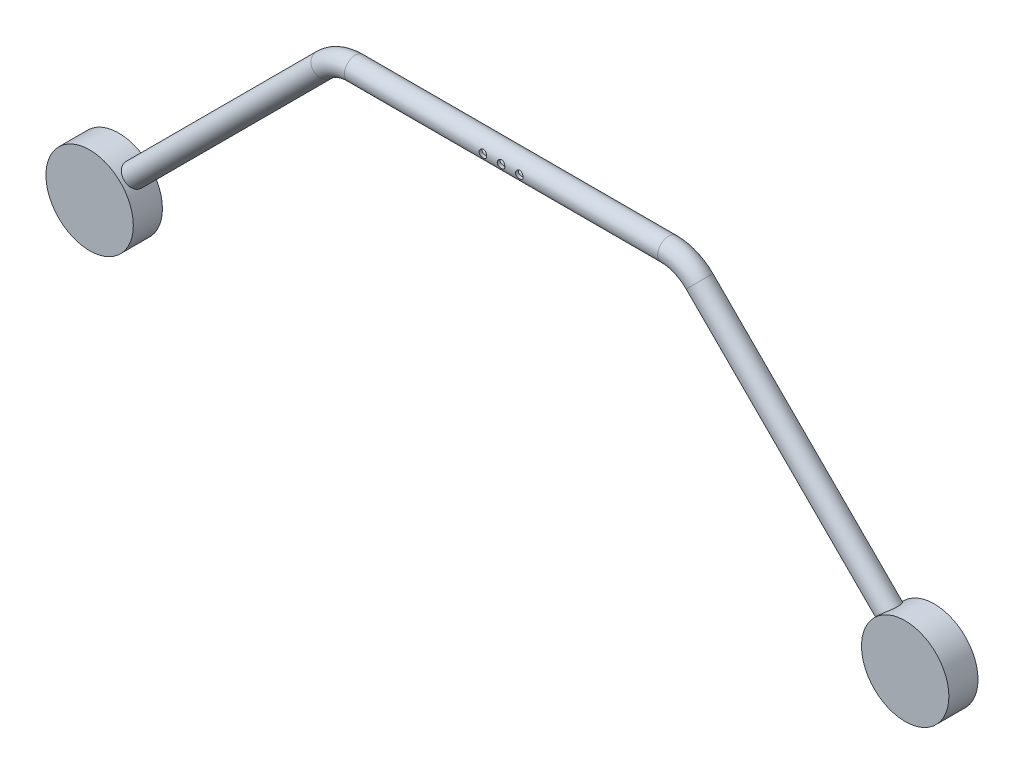
SolidWorks part; units mm, degrees
ref_plane "Front Plane" through (0, 0, 0) normal (0, 0, 1) x (1, 0, 0)
ref_plane "Top Plane" through (0, 0, 0) normal (0, 1, 0) x (1, 0, 0)
ref_plane "Right Plane" through (0, 0, 0) normal (1, 0, 0) x (0, 0, -1)
sketch "Sketch1" plane through (0, 0, 0) normal (0, 0, 1) x (1, 0, 0)
  line L10 (0, 19.4566) -> (0, -8.1997) construction
  line L11 (-355.6, -203.2) -> (-355.6, -165.1) construction
  line L12 (355.6, -203.2) -> (355.6, -165.1) construction
  circle A0 centre (-355.6, -203.2) radius 38.1
  circle A3 centre (-355.6, -203.2) radius 85.471 construction
  circle A4 centre (355.6, -203.2) radius 38.1
  circle A5 centre (355.6, -203.2) radius 85.471 construction
  point P16 (-355.6, -185.2)
  point P17 (355.6, -185.2)
  dimension "D5" = 76.2
  dimension "D6" = 170.942
  dimension "D4" = 18
  dimension "D7" = 18
  dimension "D8" = 711.2
  dimension "D1" = 203.2
extrude "Boss-Extrude1" add sketch "Sketch1" along normal blind 25.4 contours A0 | A4 | A0 | A4 region at (-355.6, -203.2, 0) region at (355.6, -203.2, 0)
ref_plane "Plane1" through (0, 0, 12.7) normal (0, 0, 1) x (1, 0, 0)
sketch "Sketch4" plane through (0, 0, 12.7) normal (0, 0, 1) x (1, 0, 0)
  line L0 (-355.6, -203.2) -> (-163.5592, -11.1592)
  line L1 (-136.6185, 0) -> (136.6185, 0)
  line L2 (163.5592, -11.1592) -> (355.6, -203.2)
  arc A0 (136.6185, 0) -> (163.5592, -11.1592) centre (136.6185, -38.1) cw
  arc A1 (-163.5592, -11.1592) -> (-136.6185, 0) centre (-136.6185, -38.1) cw
  dimension "D1" = 38.1
  dimension "D2" = 711.2
  dimension "D3" = 203.2
  dimension "D4" = 135
sweep "Sweep1" add path "Sketch4" circular profile diameter 19.05 parameters "D3"=19.05
sketch "Sketch23" plane through (0, 0, 25.4) normal (0, 0, 1) x (1, 0, 0)
  line L0 (-15.875, 0) -> (15.875, 0) construction
  dimension "D1" = 31.75
shell "Shell1" thickness 2.54 removed face at (348.8648, -209.9352, 12.7) removed face at (-348.8648, -209.9352, 12.7)
hole_wizard "M6 Clearance Hole1" positions "3DSketch1" profile "Sketch49" hole size "M6" standard "ANSI Metric" end condition through all
sketch3d "3DSketch1"
  point P0 (-15.875, 0, 22.225)
  point P2 (15.875, 0, 22.225)
sketch "Sketch49" plane through (-15.875, 0, 22.225) normal (1, 0, 0) x (0, -1, 0)
  line L0 (0, 0) -> (0, 22.225)
  line L1 (0, 22.225) -> (3.3, 22.225)
  line L2 (3.3, 22.225) -> (3.3, 0.025)
  line L3 (3.3, 0.025) -> (3.325, 0)
  line L5 (3.325, 0) -> (0, 0)
  line L6 (-3.3, 0.025) -> (-3.325, 0) construction
  line L11 (0, -6.35) -> (0, 107.95) construction
  dimension "Thru Hole Dia." = 6.6
  dimension "Thru Hole Depth" = 22.225
  dimension "Near C'Sink Dia." = 6.65
  dimension "Near C'Sink Angle" = 90
hole_wizard "M6 Clearance Hole2" positions "3DSketch2" profile "Sketch51" hole size "M6" standard "ANSI Metric" end condition through all
sketch3d "3DSketch2"
  point P0 (0, 0, 22.225)
sketch "Sketch51" plane through (0, 0, 22.225) normal (1, 0, 0) x (0, -1, 0)
  line L0 (0, 0) -> (0, 22.225)
  line L1 (0, 22.225) -> (3.3, 22.225)
  line L2 (3.3, 22.225) -> (3.3, 0.025)
  line L3 (3.3, 0.025) -> (3.325, 0)
  line L5 (3.325, 0) -> (0, 0)
  line L6 (-3.3, 0.025) -> (-3.325, 0) construction
  line L11 (0, -6.35) -> (0, 107.95) construction
  dimension "Thru Hole Dia." = 6.6
  dimension "Thru Hole Depth" = 22.225
  dimension "Near C'Sink Dia." = 6.65
  dimension "Near C'Sink Angle" = 90
equation "\"Rover_Length\"= 25in"
equation "\"Rover_Width\"= 18in"
equation "\"Rover_Height\"= 12in"
equation "\"Chassis_Wheelbase\"= 28in"
equation "\"Chassis_WheelDiam\"= 171mm"
equation "\"Chassis_ArmDiamWidth\"= 0.75in"
equation "\"Chassis_ArmAngle\"= 135deg"
equation "\"Chassis_HubMountOD\"= 3in"
equation "\"Chassis_WheelBoltHole\"= 36mm"
equation "\"Chassis_WheelBoltNum\"= 4"
equation "\"Chassis_DiffBarLength\"= 12in"
equation "\"Chassis_DiffBarWidth\"= 1in"
equation "\"Chassis_DiffBarHeight\"= 0.5in"
equation "\"Chassis_DiffLinkage_Length\"= 2.5in"
equation "\"D5@Sketch1\"=\"Chassis_HubMountOD\""
equation "\"D4@Sketch1\"=\"Chassis_WheelBoltHole\"/2"
equation "\"D7@Sketch1\"=\"Chassis_WheelBoltHole\"/2"
equation "\"D8@Sketch1\"=\"Chassis_Wheelbase\""
equation "\"D1@Boss-Extrude1\"=\"Chassis_DiffBarWidth\""
equation "\"D2@Sketch4\"=\"Chassis_Wheelbase\""
equation "\"Chassis_ArmHeight\"= 8in"
equation "\"Chassis_MountBracketThickness\"= 0.125in"
equation "\"Chassis_MountBracketWidth\"= 3in"
equation "\"Chassis_MountBacketOverlap\"= 0.5in"
equation "\"Chassis_ArmShaftDiam\"= 0.75in"
equation "\"D3@Sketch4\"=\"Chassis_ArmHeight\""
equation "\"D4@Sketch4\"=\"Chassis_ArmAngle\""
equation "\"D1@Sketch1\"=\"Chassis_ArmHeight\""
equation "\"Chassis_ArmHoleSpacing\"= 1.25in"
equation "\"D1@Sketch23\"=\"Chassis_ArmHoleSpacing\""
